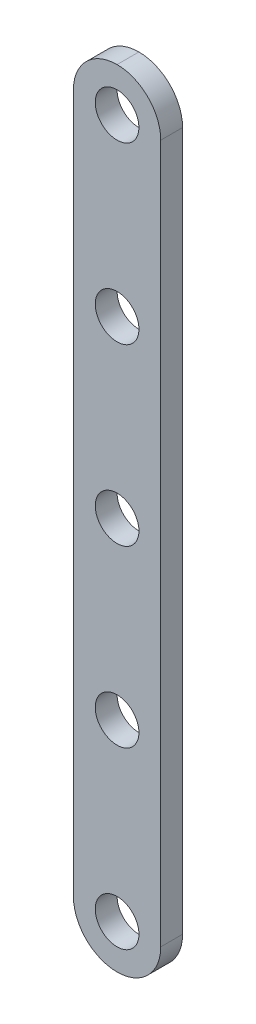
SolidWorks part; units mm, degrees
ref_plane "前视基准面" through (0, 0, 0) normal (0, 0, 1) x (1, 0, 0)
ref_plane "上视基准面" through (0, 0, 0) normal (0, 1, 0) x (1, 0, 0)
ref_plane "右视基准面" through (0, 0, 0) normal (1, 0, 0) x (0, 0, -1)
sketch "草图1" plane through (0, 0, 0) normal (0, 0, 1) x (1, 0, 0)
  line L0 (0, 0) -> (0, -80) construction
  line L1 (-10, -90) -> (10, -90)
  line L2 (-10, -90) -> (-10, 90)
  line L3 (-10, 90) -> (10, 90)
  line L4 (10, -90) -> (10, 90)
  line L5 (-10, -90) -> (10, 90) construction
  line L6 (-10, 90) -> (10, -90) construction
  line L7 (-10, 0) -> (10, 0) construction
  line L8 (0, -80) -> (0, 80) construction
  circle A0 centre (0, -80) radius 5
  circle A1 centre (0, 80) radius 5
  circle A2 centre (0, 0) radius 5
  circle A4 centre (0, -40) radius 5
  circle A5 centre (0, 40) radius 5
  point P0 (0, 0)
  dimension "D3" = 10
  dimension "D5" = 10
  dimension "D6" = 10
  dimension "D7" = 10
  dimension "D8" = 40
  dimension "D1" = 180
  dimension "D2" = 20
  dimension "D4" = 80
extrude "凸台-拉伸1" add sketch "草图1" along normal blind 5
fillet "圆角1" radius 10 4 edges at (-10, -90, 2.5) (10, -90, 2.5) (10, 90, 2.5) (-10, 90, 2.5)
